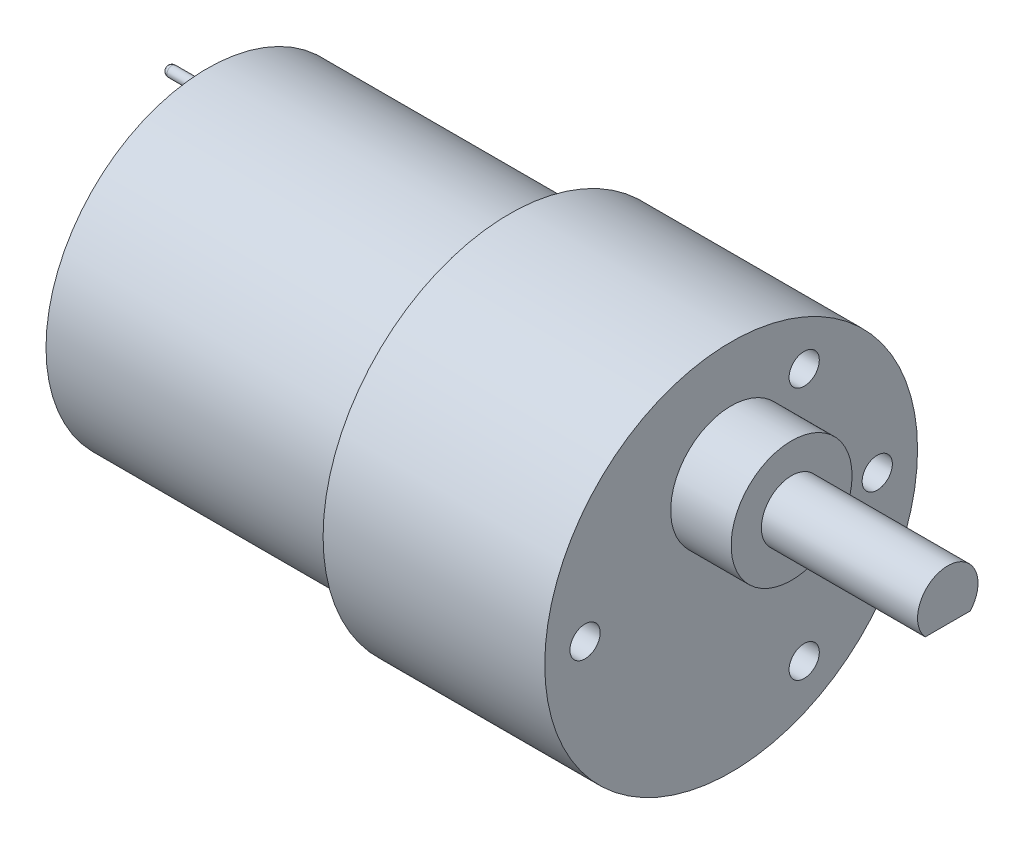
SolidWorks part; units mm, degrees
material "201.0-T43 Insulated Mold Casting (SS)"
ref_plane "Front Plane" through (0, 0, 0) normal (0, 0, 1) x (1, 0, 0)
ref_plane "Top Plane" through (0, 0, 0) normal (0, 1, 0) x (1, 0, 0)
ref_plane "Right Plane" through (0, 0, 0) normal (1, 0, 0) x (0, 0, -1)
sketch "Sketch1" plane through (0, 0, 0) normal (0, 1, 0) x (1, 0, 0)
  line L0 (0, 0) -> (52, 0)
  line L1 (0, 0) -> (-2, 0)
  line L2 (0, 0) -> (0, 16)
  line L3 (0, 16) -> (30, 16)
  line L4 (30, 16) -> (30, 18.5)
  line L5 (30, 18.5) -> (52, 18.5)
  line L6 (52, 18.5) -> (52, 0)
revolve "Revolve1" add sketch "Sketch1" angle 360 about L0 region at (26.9301, 0, -8.5736)
sketch "Sketch2" plane through (0, 0, 0) normal (-1, 0, 0) x (0, 0, 1)
  circle A0 centre (0, 0) radius 2
extrude "Boss-Extrude1" add sketch "Sketch2" along normal blind 2
fillet "Fillet3" radius 2 1 edges at (-2, 0, 2)
sketch "Sketch3" plane through (52, 0, 0) normal (1, 0, 0) x (0, 0, -1)
  line L0 (0, 0) -> (0, 7)
  circle A0 centre (0, 7) radius 6
extrude "Boss-Extrude2" add sketch "Sketch3" along normal blind 6 contours A0 region at (52, 2.8774, -4.1226)
sketch "Sketch4" plane through (58, 0, 0) normal (1, 0, 0) x (0, 0, -1)
  line L0 (0, 0) -> (0, 7)
  circle A0 centre (0, 7) radius 3
extrude "Boss-Extrude3" add sketch "Sketch4" along normal blind 15.5 contours A0 region at (58, 4.9387, -2.0613)
sketch "Sketch5" plane through (73.5, 0, 0) normal (1, 0, 0) x (0, 0, -1)
  line L0 (0, 0) -> (0, 5)
  line L1 (0, 5) -> (2.2361, 5)
  line L2 (2.2361, 5) -> (2.2361, 4)
  line L3 (2.2361, 4) -> (0, 4)
  line L4 (0, 5) -> (-2.2361, 5)
  line L5 (-2.2361, 5) -> (-2.2361, 4)
  line L6 (-2.2361, 4) -> (0, 4)
  circle A0 centre (0, 7) radius 3 construction
  circle A1 centre (0, 7) radius 3 construction
  circle M1 centre (0, 7) radius 3
extrude "Cut-Extrude1" cut sketch "Sketch5" against normal blind 12 contours L0 L4 M1 | L1 L0 M1 region at (73.5, 4.5937, 0.8609) region at (73.5, 4.5937, -0.8609)
sketch "Sketch6" plane through (52, 0, 0) normal (1, 0, 0) x (0, 0, -1)
  circle A0 centre (-14.5, 0) radius 1.5
  circle A1 centre (0, 0) radius 14.5
  circle A2 centre (7.25, 12.5574) radius 1.5
  circle A3 centre (7.25, -12.5574) radius 1.5
  point P12 (0, 0)
  dimension "D1" = 3
extrude "Cut-Extrude2" cut sketch "Sketch6" against normal blind 5 contours A2 | A3 | A0
sketch "Sketch7" plane through (52, 0, 0) normal (1, 0, 0) x (0, 0, -1)
  line L0 (0, 0) -> (14.5, 0)
  circle A0 centre (14.5, 0) radius 1.5
extrude "Cut-Extrude3" cut sketch "Sketch7" against normal blind 5 contours A0
sketch "Sketch9" plane through (0, 0, 0) normal (-1, 0, 0) x (0, 0, 1)
  line L0 (0, 0) -> (0, 14)
  line L1 (0, 0) -> (0, -14)
  circle A0 centre (0, 14) radius 0.5
  circle A1 centre (0, -14) radius 0.5
extrude "Boss-Extrude4" add sketch "Sketch9" along normal blind 4 contours A0 | A1
fillet "Fillet4" radius 0.5 2 edges at (-4, -14, 0.5) (-4, 14, 0.5)
